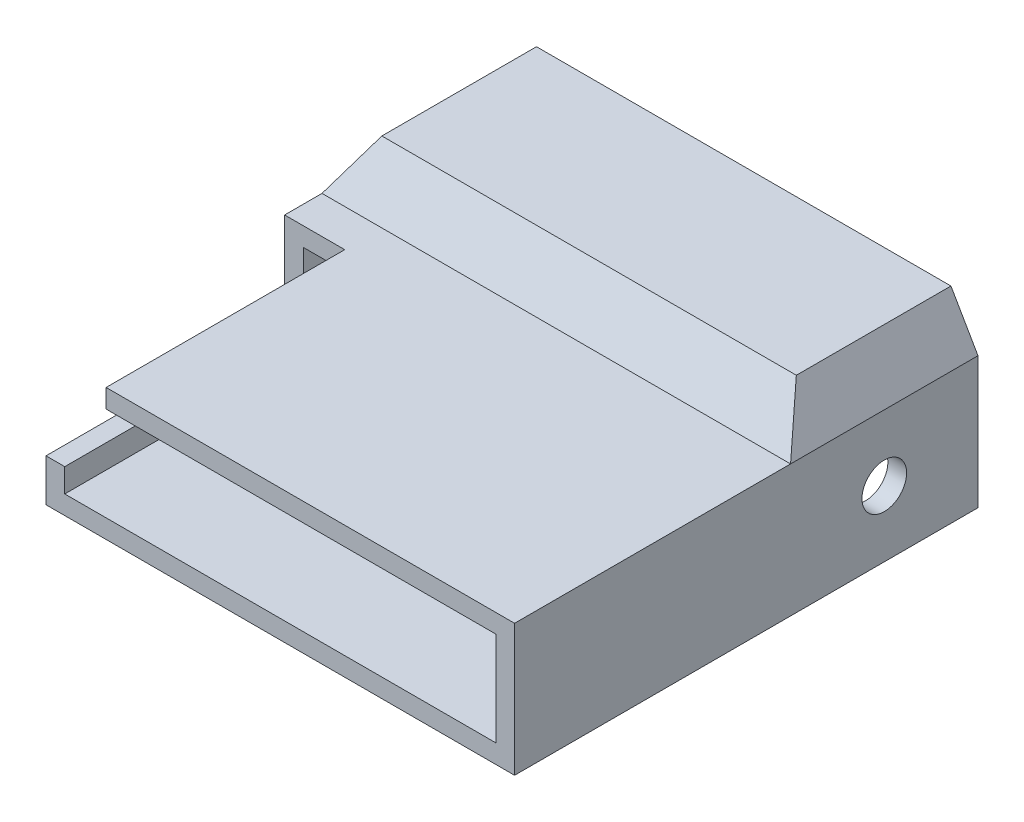
SolidWorks part; units mm, degrees
ref_plane "Front Plane" through (0, 0, 0) normal (0, 0, 1) x (1, 0, 0)
ref_plane "Top Plane" through (0, 0, 0) normal (0, 1, 0) x (1, 0, 0)
ref_plane "Right Plane" through (0, 0, 0) normal (1, 0, 0) x (0, 0, -1)
sketch "Sketch1" plane through (0, 0, 0) normal (0, 1, 0) x (1, 0, 0)
  line L1 (0, 0) -> (100, 0)
  line L2 (0, 0) -> (0, 98.9)
  line L3 (0, 98.9) -> (100, 98.9)
  line L4 (100, 0) -> (100, 98.9)
  dimension "D1" = 98.9
  dimension "D2" = 100
extrude "Boss-Extrude1" add sketch "Sketch1" along normal blind 28.1 contours L1 L4 L3 L2
shell "Shell1" thickness 4 removed face at (50, 14.05, -98.9) removed face at (50, 14.05, 0)
sketch "Sketch4" plane through (0, 0, 0) normal (0, -1, 0) x (1, 0, 0)
  line L1 (0, 0) -> (12.827, 0)
  line L2 (0, 0) -> (0, -50.927)
  line L3 (0, -50.927) -> (12.827, -50.927)
  line L4 (12.827, 0) -> (12.827, -50.927)
  dimension "D1" = 50.927
  dimension "D2" = 12.827
extrude "Cut-Extrude3" cut sketch "Sketch4" against normal through all from offset 9.05 offset against normal yes
sketch "Sketch5" plane through (0, 28.1, 0) normal (0, 1, 0) x (1, 0, 0)
  line L17 (100, 0) -> (100, 98.9) construction
  line L23 (0, 50.927) -> (0, 98.9) construction
  line L24 (21.5, 98.9) -> (8.5, 98.9)
  line L25 (21.5, 98.9) -> (21.5, 73.9)
  line L26 (21.5, 73.9) -> (8.5, 73.9)
  line L27 (8.5, 98.9) -> (8.5, 73.9)
  line L28 (21.5, 98.9) -> (8.5, 73.9) construction
  line L29 (21.5, 73.9) -> (8.5, 98.9) construction
  line L30 (44.8333, 98.9) -> (31.8333, 98.9)
  line L31 (44.8333, 98.9) -> (44.8333, 73.9)
  line L32 (44.8333, 73.9) -> (31.8333, 73.9)
  line L33 (31.8333, 98.9) -> (31.8333, 73.9)
  line L34 (44.8333, 98.9) -> (31.8333, 73.9) construction
  line L35 (44.8333, 73.9) -> (31.8333, 98.9) construction
  line L36 (68.1667, 98.9) -> (55.1667, 98.9)
  line L37 (68.1667, 98.9) -> (68.1667, 73.9)
  line L38 (68.1667, 73.9) -> (55.1667, 73.9)
  line L39 (55.1667, 98.9) -> (55.1667, 73.9)
  line L40 (68.1667, 98.9) -> (55.1667, 73.9) construction
  line L41 (68.1667, 73.9) -> (55.1667, 98.9) construction
  line L42 (91.5, 98.9) -> (78.5, 98.9)
  line L43 (91.5, 98.9) -> (91.5, 73.9)
  line L44 (91.5, 73.9) -> (78.5, 73.9)
  line L45 (78.5, 98.9) -> (78.5, 73.9)
  line L46 (91.5, 98.9) -> (78.5, 73.9) construction
  line L47 (91.5, 73.9) -> (78.5, 98.9) construction
  line L48 (15, 86.4) -> (85, 86.4) construction
  line L49 (0, 98.9) -> (100, 98.9) construction
  point P6 (15, 86.4)
  point P7 (38.3333, 86.4)
  point P8 (61.6667, 86.4)
  point P9 (85, 86.4)
  point P10 (38.3333, 86.4)
  point P11 (61.6667, 86.4)
  point P12 (15, 86.4)
  point P17 (38.3333, 86.4)
  point P22 (61.6667, 86.4)
  point P27 (85, 86.4)
  dimension "D1" = 15
  dimension "D2" = 13
  dimension "D4" = 15
  dimension "D3" = 25
extrude "Cut-Extrude4" cut sketch "Sketch5" against normal through all
sketch "Sketch6" plane through (0, 0, 0) normal (-1, 0, 0) x (0, 0, 1)
  line L0 (-98.9, 28.1) -> (-98.9, 0) construction
  line L2 (-80.4, 21.8125) -> (-77.4, 21.8125)
  line L3 (-80.4, 21.8125) -> (-80.4, 15.8125)
  line L4 (-80.4, 15.8125) -> (-77.4, 15.8125)
  line L5 (-77.4, 21.8125) -> (-77.4, 15.8125)
  line L6 (-80.4, 21.8125) -> (-77.4, 15.8125) construction
  line L7 (-80.4, 15.8125) -> (-77.4, 21.8125) construction
  circle A0 centre (-78.9, 14.05) radius 4.7625
  point P4 (-78.9, 18.8125)
  point P6 (-98.9, 14.05)
  dimension "D1" = 9.525
  dimension "0.25" = 20
  dimension "D2" = 3
  dimension "D3" = 3
extrude "Cut-Extrude5" cut sketch "Sketch6" against normal through all and the other way blind 4.2672 contours L3 A0 L5 L4 | L5 A0 L3 L4 region at (0, 17.2734, -78.9) region at (0, 13.5982, -78.9)
extrude "Boss-Extrude3" add sketch "Sketch6<3>" against normal up to surface (4 mm away) contours L5 A0 L3 L4 region at (0, 17.2734, -78.9) up to face at (4, 14.05, -74.1375)
sketch "Sketch6<3>" plane through (0, 0, 0) normal (-1, 0, 0) x (0, 0, 1) same geometry as "Sketch6"
sketch "Sketch12" plane through (0, 28.1, 0) normal (0, 1, 0) x (1, 0, 0)
  line L0 (100, 0) -> (100, 98.9) construction
  line L1 (0, 98.9) -> (100, 98.9)
  line L2 (0, 98.9) -> (0, 58.9)
  line L3 (0, 58.9) -> (100, 58.9)
  line L4 (100, 98.9) -> (100, 58.9)
  dimension "D1" = 40
extrude "Boss-Extrude11" add sketch "Sketch12" along normal blind 10 and the other way blind 1
sketch "Sketch13" plane through (0, 0, -98.9) normal (0, 0, -1) x (-1, 0, 0)
  line L0 (-68.1667, 24.1) -> (-55.1667, 24.1)
  line L1 (-91.5, 24.1) -> (-78.5, 24.1)
  line L2 (-91.5, 24.1) -> (-91.5, 33.1)
  line L3 (-91.5, 33.1) -> (-78.5, 33.1)
  line L4 (-78.5, 24.1) -> (-78.5, 33.1)
  line L5 (-68.1667, 24.1) -> (-68.1667, 33.1)
  line L6 (-68.1667, 33.1) -> (-55.1667, 33.1)
  line L7 (-55.1667, 24.1) -> (-55.1667, 33.1)
  line L8 (-68.1667, 24.1) -> (-55.1667, 24.1) construction
  line L9 (-68.1667, 24.1) -> (-68.1667, 27.1) construction
  line L10 (-44.8333, 24.1) -> (-31.8333, 24.1)
  line L11 (-44.8333, 24.1) -> (-44.8333, 33.1)
  line L12 (-44.8333, 33.1) -> (-31.8333, 33.1)
  line L13 (-31.8333, 24.1) -> (-31.8333, 33.1)
  line L14 (-44.8333, 24.1) -> (-44.8333, 27.1) construction
  line L15 (-21.5, 24.1) -> (-31.8333, 24.1) construction
  line L16 (-21.5, 24.1) -> (-8.5, 24.1)
  line L17 (-21.5, 24.1) -> (-21.5, 33.1)
  line L18 (-21.5, 33.1) -> (-8.5, 33.1)
  line L19 (-8.5, 24.1) -> (-8.5, 33.1)
  line L20 (-21.5, 24.1) -> (-21.5, 27.1) construction
  line L21 (-4, 24.1) -> (-8.5, 24.1) construction
  dimension "D1" = 9
  dimension "D2" = 13
extrude "Cut-Extrude6" cut sketch "Sketch13" against normal blind 35
fillet "Fillet2" radius 10 4 edges at (15, 33.1, -63.9) (38.3333, 33.1, -63.9) (61.6667, 33.1, -63.9) (85, 33.1, -63.9)
chamfer "Chamfer1" distance 10 angle 35 1 edges at (50, 38.1, -58.9) first distance on face at (50, 33.1, -58.9)
chamfer "Chamfer2" distance 10 angle 30 2 edges at (0, 38.1, -82.401) (100, 38.1, -82.401) first distance on face at (0, 18.8125, -53.057) first distance on face at (100, 22.0667, -53.767)
sketch "Sketch14" plane through (0, 24.1, 0) normal (0, -1, 0) x (1, 0, 0)
  line L1 (68.1667, -98.9) -> (73.3333, -98.9)
  line L2 (68.1667, -98.9) -> (68.1667, -93.9)
  line L3 (68.1667, -93.9) -> (73.3333, -93.9)
  line L4 (73.3333, -98.9) -> (73.3333, -93.9)
  dimension "D1" = 5
  dimension "D2" = 5.1667
extrude "Boss-Extrude12" add sketch "Sketch14" along normal blind 10
sketch "Sketch15" plane through (73.3333, 0, 0) normal (1, 0, 0) x (0, 0, -1)
  line L0 (98.9, 14.1) -> (93.9, 14.1) construction
  line L1 (98.9, 14.1) -> (98.9, 24.1) construction
  circle A0 centre (96.4, 17.1) radius 1
  dimension "D1" = 2
  dimension "D2" = 3
  dimension "D3" = 2.5
extrude "Boss-Extrude13" add sketch "Sketch15" along normal blind 5
